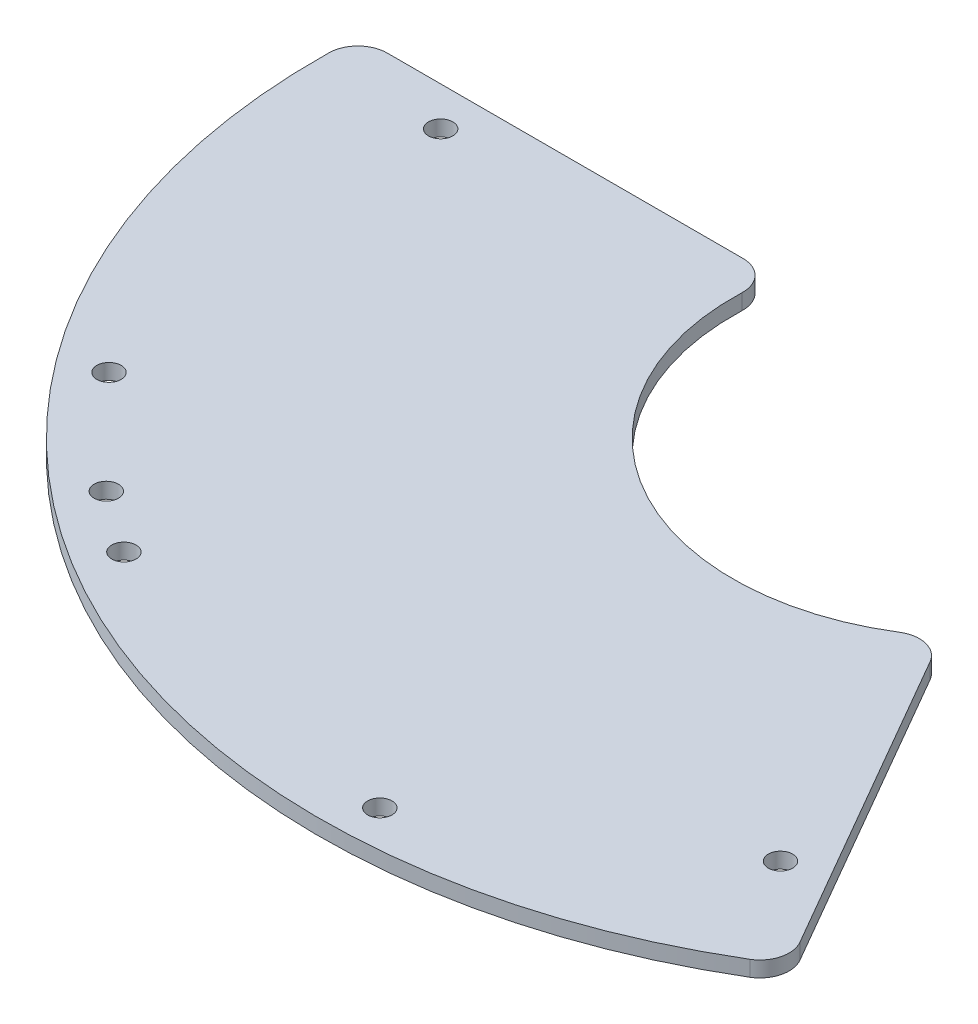
SolidWorks part; units mm, degrees
material "Thornel VCB-20 Carbon Cloth"
ref_plane "Front Plane" through (0, 0, 0) normal (0, 0, 1) x (1, 0, 0)
ref_plane "Top Plane" through (0, 0, 0) normal (0, 1, 0) x (1, 0, 0)
ref_plane "Right Plane" through (0, 0, 0) normal (1, 0, 0) x (0, 0, -1)
sketch "Sketch1" plane through (0, 0, 0) normal (0, 1, 0) x (1, 0, 0)
  line L0 (0, 0) -> (84.7962, 0) construction
  line L1 (0, 0) -> (33.75, -58.4567) construction
  line L2 (0, 0) -> (-67.5, 0) construction
  line L3 (-67.3814, 4) -> (-24.6779, 4)
  line L4 (37.1548, -56.354) -> (15.8031, -19.3717)
  line L5 (0, 0) -> (2.2161, -63.4613) construction
  line L6 (0, 0) -> (-33.6499, -53.8511) construction
  line L7 (0, 0) -> (-50.3779, -38.6564) construction
  line L8 (-39.9618, -49.3488) -> (0, 0) construction
  arc A0 (-67.3814, 4) -> (37.1548, -56.354) centre (0, 0) ccw
  arc A1 (-24.6779, 4) -> (15.8031, -19.3717) centre (0, 0) ccw
  circle A2 centre (0, 0) radius 55 construction
  circle A3 centre (-55, 0) radius 1.25
  circle A4 centre (27.5, -47.6314) radius 1.25
  circle A5 centre (0, 0) radius 63.5 construction
  circle A6 centre (2.2161, -63.4613) radius 1.25
  circle A7 centre (-33.6499, -53.8511) radius 1.25
  circle A8 centre (-39.9618, -49.3488) radius 1.25
  circle A9 centre (-50.3779, -38.6564) radius 1.25
  dimension "D1" = 50
  dimension "D2" = 135
  dimension "D3" = 110
  dimension "D7" = 2.5
  dimension "D5" = 4
  dimension "D6" = 4
  dimension "D8" = 4
  dimension "D9" = 28
  dimension "D10" = 62
  dimension "D11" = 69
  dimension "D12" = 82.5
  dimension "D4" = 120
  dimension "D17" = 88
  dimension "D18" = 122
  dimension "D19" = 129
  dimension "D20" = 142.5
extrude "Boss-Extrude1" add sketch "Sketch1" along normal mid plane 1.6
fillet "Fillet1" radius 3 4 edges at (-67.3814, 0, -4) (-24.6779, 0, -4) (37.1548, 0, 56.354) (15.8031, 0, 19.3717)
equation "\"pcb_mount_circle_diameter\"= 110mm"
equation "\"outer_diameter\"= 135mm"
equation "\"inner_diameter\"= 50mm"
equation "\"D1@Sketch1\"=\"inner_diameter\""
equation "\"D2@Sketch1\"=\"outer_diameter\""
equation "\"D3@Sketch1\"=\"pcb_mount_circle_diameter\""
equation "\"D6@Sketch1\"=\"D5@Sketch1\""
